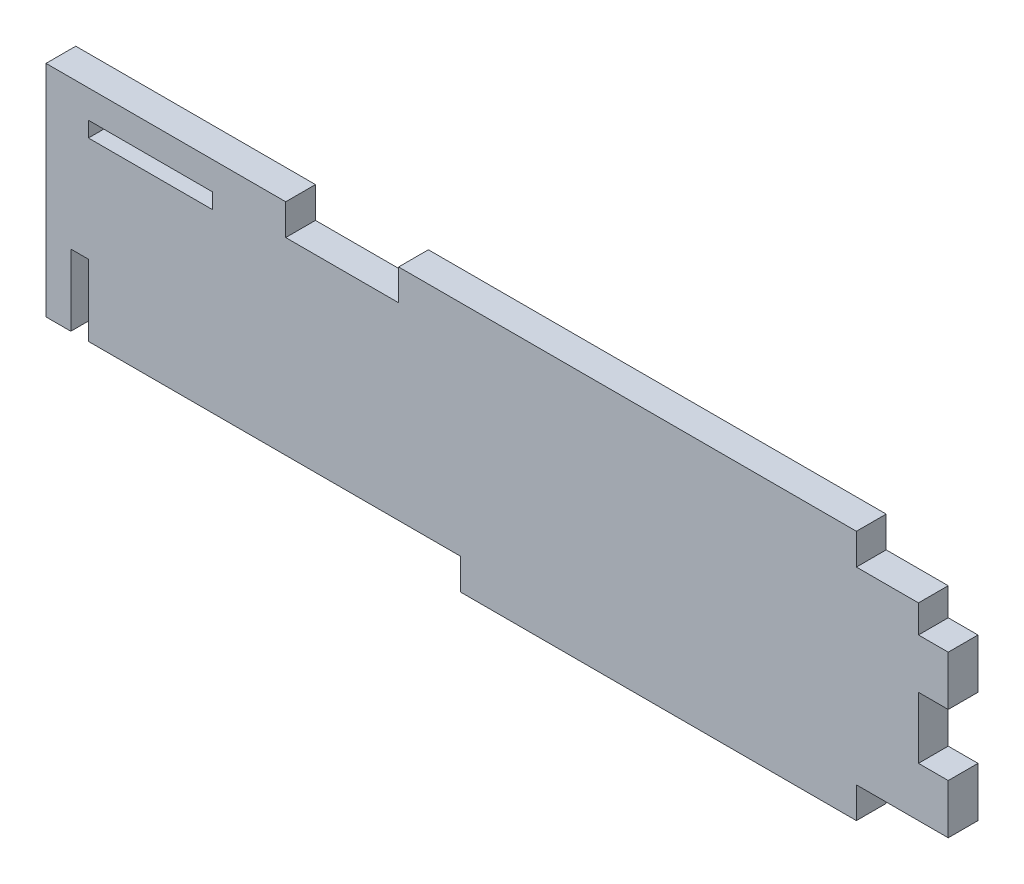
SolidWorks part; units mm, degrees
ref_plane "Front Plane" through (0, 0, 0) normal (0, 0, 1) x (1, 0, 0)
ref_plane "Top Plane" through (0, 0, 0) normal (0, 1, 0) x (1, 0, 0)
ref_plane "Right Plane" through (0, 0, 0) normal (1, 0, 0) x (0, 0, -1)
sketch "Sketch1" plane through (0, 0, 0) normal (0, 0, 1) x (1, 0, 0)
  line L0 (-6.35, 4.7244) -> (3.048, 4.7244) construction
  line L1 (-6.35, 4.7244) -> (-6.35, 1.5494) construction
  line L2 (-6.35, 1.5494) -> (-46.863, 1.5494) construction
  line L3 (-46.863, 1.5494) -> (-46.863, 4.7244) construction
  line L4 (-84.963, 24.3332) -> (-84.963, 22.7584) construction
  line L5 (-84.963, 22.7584) -> (-72.263, 22.7584) construction
  line L6 (-72.263, 22.7584) -> (-72.263, 24.3332) construction
  line L10 (-84.963, 24.3332) -> (-84.963, 22.7584)
  line L12 (-84.963, 22.7584) -> (-72.263, 22.7584)
  line L13 (-72.263, 22.7584) -> (-72.263, 24.3332)
  line L14 (-6.35, 27.2034) -> (-53.213, 27.2034) construction
  line L15 (-6.35, 24.0284) -> (-6.35, 27.2034) construction
  line L16 (0, 24.0284) -> (-6.35, 24.0284) construction
  line L17 (0, 24.0284) -> (0, 21.1836) construction
  line L18 (3.048, 21.1836) -> (0, 21.1836) construction
  line L19 (3.048, 21.1836) -> (3.048, 16.1036) construction
  line L20 (3.048, 16.1036) -> (0, 16.1036) construction
  line L21 (0, 16.1036) -> (0, 9.8044) construction
  line L22 (3.048, 9.8044) -> (0, 9.8044) construction
  line L23 (3.048, 9.8044) -> (3.048, 4.7244) construction
  line L24 (-6.35, 4.7244) -> (3.048, 4.7244)
  line L25 (-6.35, 4.7244) -> (-6.35, 1.5494)
  line L26 (-6.35, 1.5494) -> (-46.863, 1.5494)
  line L27 (-46.863, 1.5494) -> (-46.863, 4.7244)
  line L28 (-84.963, 4.7244) -> (-46.863, 4.7244)
  line L29 (-89.3064, 15.9639) -> (-89.3064, 4.7244)
  line L30 (-89.3064, 4.7244) -> (-86.7664, 4.7244)
  line L32 (-86.7664, 4.7244) -> (-86.7664, 12.0142)
  line L33 (-64.77, 24.0284) -> (-53.213, 24.0284)
  line L34 (-86.7664, 12.0142) -> (-84.963, 12.0142)
  line L35 (-84.963, 12.0142) -> (-84.963, 4.7244)
  line L36 (-72.263, 24.3332) -> (-84.963, 24.3332)
  line L37 (-53.213, 27.2034) -> (-53.213, 24.0284)
  line L38 (-6.35, 27.2034) -> (-53.213, 27.2034)
  line L39 (-6.35, 24.0284) -> (-6.35, 27.2034)
  line L40 (0, 24.0284) -> (-6.35, 24.0284)
  line L41 (0, 24.0284) -> (0, 21.1836)
  line L42 (3.048, 21.1836) -> (0, 21.1836)
  line L43 (3.048, 21.1836) -> (3.048, 16.1036)
  line L44 (3.048, 16.1036) -> (0, 16.1036)
  line L45 (0, 16.1036) -> (0, 9.8044)
  line L46 (3.048, 9.8044) -> (0, 9.8044)
  line L47 (3.048, 9.8044) -> (3.048, 4.7244)
  line L48 (-89.3064, 4.7244) -> (-89.3064, 27.2034) construction
  line L49 (-89.3064, 27.2034) -> (-64.77, 27.2034) construction
  line L50 (-64.77, 27.2034) -> (-64.77, 24.0284) construction
  line L51 (-89.3064, 4.7244) -> (-89.3064, 27.2034)
  line L52 (-89.3064, 27.2034) -> (-64.77, 27.2034)
  line L53 (-64.77, 27.2034) -> (-64.77, 24.0284)
extrude "Boss-Extrude1" add sketch "Sketch1" along normal blind 3.048 contours L47 L46 L45 L44 L43 L42 L41 L40 L39 L38 L37 L29 L30 L32 L34 L28 L27 L26 L25 L24 region at (-42.4087, 14.8356, 0)
sketch "Sketch2" plane through (0, 0, 3.048) normal (0, 0, 1) x (1, 0, 0)
  line L1 (-72.263, 24.3332) -> (-84.963, 24.3332) construction
  line L2 (-84.963, 24.3332) -> (-72.263, 24.3332)
  line L3 (-84.963, 24.3332) -> (-84.963, 24.4348)
  line L4 (-84.963, 24.4348) -> (-72.263, 24.4348)
  line L6 (-72.263, 24.3332) -> (-72.263, 24.4348)
  line L7 (-84.963, 22.7584) -> (-72.263, 22.7584) construction
  dimension "D1" = 1.6764
extrude "Boss-Extrude2" add sketch "Sketch2" against normal up to vertex (3.048 mm away) up to point (-64.77, 27.2034, 0)
